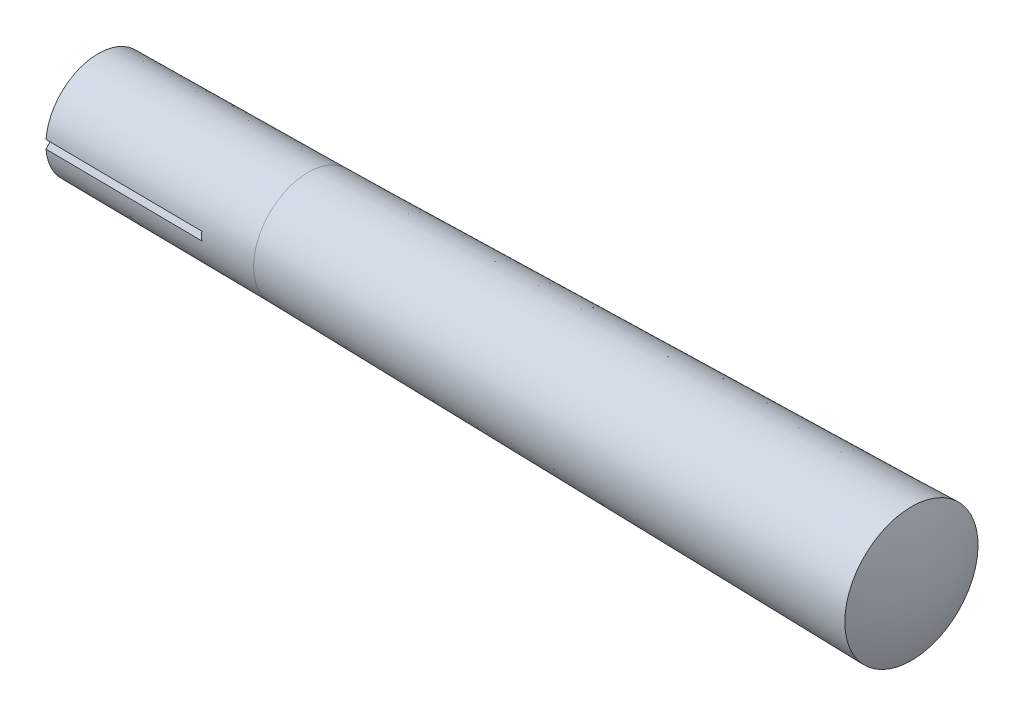
SolidWorks part; units mm, degrees
ref_plane "Front Plane" through (0, 0, 0) normal (0, 0, 1) x (1, 0, 0)
ref_plane "Top Plane" through (0, 0, 0) normal (0, 1, 0) x (1, 0, 0)
ref_plane "Right Plane" through (0, 0, 0) normal (1, 0, 0) x (0, 0, -1)
sketch "BodySke" plane through (0, 0, 0) normal (0, 0, 1) x (1, 0, 0)
  line L0 (0, 0) -> (250, 0) construction
  line L1 (0, 0) -> (250, 5) construction
  line L2 (250, 5) -> (250, 0) construction
  line L3 (0, 0) -> (0, 10) construction
  line L4 (0, 10) -> (40, 10.4)
  line L5 (40, 10.4) -> (155.01, 12.7002)
  line L7 (0, 0) -> (-21.989, 0) construction
  line L8 (0, -10) -> (40, -10.4) construction
  line L9 (40, -10.4) -> (155.01, -12.7002) construction
  line L10 (-2.5, 0) -> (157.5, 0)
  line L11 (157.5, 0) -> (157.5, 15.9181) construction
  arc A0 (0, 10) -> (-2.5, 0) centre (17.4975, 0.3131) ccw
  arc A1 (155.01, 12.7002) -> (157.5, 0) centre (123.8664, 0) cw
  dimension "D6" = 20
  dimension "D1" = 5
  dimension "D2" = 250
  dimension "D5" = 40
  dimension "Length" = 160
  dimension "D3" = 2.49
revolve "BaseBody" add sketch "BodySke" angle 360 about L0
sketch "SplSke" plane through (0, 0, 0) normal (1, 0, 0) x (0, 0, -1)
  line L0 (12.7002, 0.8) -> (12.7002, -0.8)
  line L1 (12.7002, 0.8) -> (-12.7002, 0.8)
  line L2 (-12.7002, 0.8) -> (-12.7002, -0.8)
  line L3 (12.7002, -0.8) -> (-12.7002, -0.8)
  circle A0 centre (0, 0) radius 12.7002 construction
  dimension "D1" = 0.8
extrude "Split" cut sketch "SplSke" along normal blind 30 and the other way through all
equation "\"D1@BodySke\" = \"D2@BodySke\" / 50"
equation "\"D5@BodySke\" = \"Diameter@BodySke\" * 2"
equation "\"D6@BodySke\" = \"Diameter@BodySke\""
equation "\"D1@SplSke\" = \"Split_Width@SplSke\" / 2"
equation "\"D3@BodySke\" = \"Radius_height@BodySke\" - 0.01"
